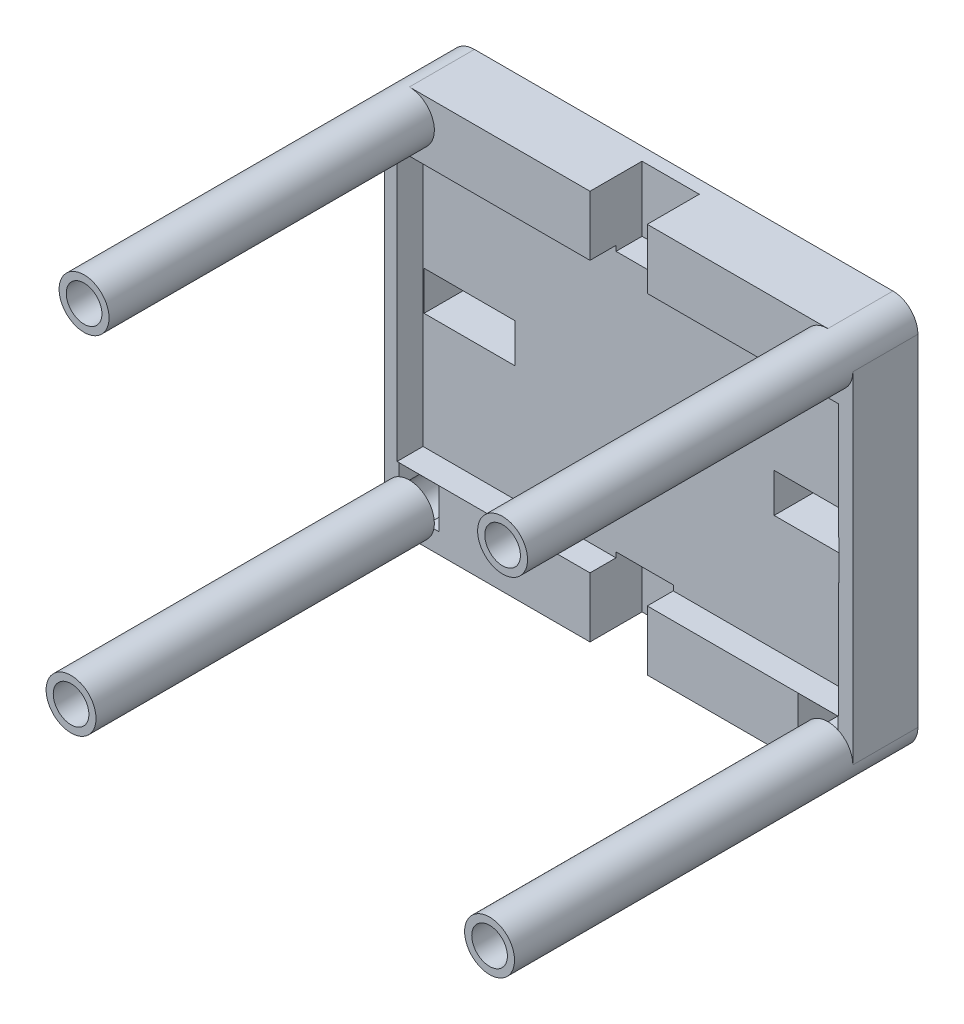
SolidWorks part; units mm, degrees
ref_plane "Front Plane" through (0, 0, 0) normal (0, 0, 1) x (1, 0, 0)
ref_plane "Top Plane" through (0, 0, 0) normal (0, 1, 0) x (1, 0, 0)
ref_plane "Right Plane" through (0, 0, 0) normal (1, 0, 0) x (0, 0, -1)
other "Configuration Table"
sketch "草图1" plane through (0, 0, 0) normal (0, 0, 1) x (1, 0, 0)
  line L0 (0, 0) -> (83.8895, 0) construction
  line L1 (-80.4073, 75) -> (80.4073, 75)
  line L2 (-90, 65.4073) -> (-90, -65.4073)
  line L3 (-80.4073, -75) -> (80.4073, -75)
  line L4 (90, 65.4073) -> (90, -65.4073)
  line L5 (-90, 75) -> (90, -75) construction
  line L6 (-90, -75) -> (90, 75) construction
  line L7 (0, 0) -> (0, -55.7173) construction
  line L8 (-85.1459, 52) -> (-7.782, 52)
  line L9 (-85.1459, -52) -> (-7.782, -52)
  line L10 (-85.1459, 52) -> (-85.1459, -52)
  line L11 (84.4384, -52) -> (84.4384, 52)
  line L14 (7.782, 52) -> (84.4384, 52)
  line L15 (7.782, -52) -> (84.4384, -52)
  line L16 (-46.464, 52) -> (-46.464, -52) construction
  line L17 (46.1102, -52) -> (46.1102, 52) construction
  line L18 (-7.782, 52) -> (7.782, 52)
  line L20 (-7.782, -52) -> (7.782, -52)
  line L21 (-49.7645, 7.5) -> (-49.7645, -7.5)
  line L22 (84.7645, 7.5) -> (49.7645, 7.5)
  line L23 (84.7645, 7.5) -> (84.7645, -7.5)
  line L24 (84.7645, -7.5) -> (49.7645, -7.5)
  line L25 (49.7645, 7.5) -> (49.7645, -7.5)
  line L26 (84.7645, 7.5) -> (49.7645, -7.5) construction
  line L27 (84.7645, -7.5) -> (49.7645, 7.5) construction
  line L28 (-84.7645, -7.5) -> (-49.7645, -7.5)
  line L29 (-84.7645, 7.5) -> (-49.7645, 7.5)
  line L30 (-84.7645, 7.5) -> (-84.7645, -7.5)
  line L31 (84.3918, -67.3175) -> (68.9601, -67.3175)
  line L32 (11, -50) -> (-11, -50)
  line L33 (11, -50) -> (11, -75)
  line L34 (11, -75) -> (-11, -75)
  line L35 (-11, -50) -> (-11, -75)
  line L36 (11, -50) -> (-11, -75) construction
  line L37 (11, -75) -> (-11, -50) construction
  line L38 (-84.3918, -52.0059) -> (-68.9601, -52.0059)
  line L39 (-84.3918, -52.0059) -> (-84.3918, -67.3175)
  line L40 (-84.3918, -67.3175) -> (-68.9601, -67.3175)
  line L41 (-68.9601, -52.0059) -> (-68.9601, -67.3175)
  line L42 (-84.3918, -52.0059) -> (-68.9601, -67.3175) construction
  line L43 (-84.3918, -67.3175) -> (-68.9601, -52.0059) construction
  line L44 (68.9601, -52.0059) -> (68.9601, -67.3175)
  line L45 (84.3918, -52.0059) -> (84.3918, -67.3175)
  line L46 (84.4384, -52) -> (84.3918, -52.0059)
  line L47 (68.9601, -52.0059) -> (84.3918, -52.0059)
  arc A1 (-80.4073, 75) -> (-90, 65.4073) centre (-80.4073, 65.4073) ccw
  arc A2 (80.4073, 75) -> (90, 65.4073) centre (80.4073, 65.4073) cw
  arc A3 (-80.4073, -75) -> (-90, -65.4073) centre (-80.4073, -65.4073) cw
  arc A4 (80.4073, -75) -> (90, -65.4073) centre (80.4073, -65.4073) ccw
  circle A9 centre (-80.4073, 65.4073) radius 9.5927
  circle A10 centre (80.4073, 65.4073) radius 9.5927
  circle A11 centre (-80.4073, -65.4073) radius 9.5927
  circle A12 centre (80.4073, -65.4073) radius 9.5927
  circle A17 centre (-80.4073, 65.4073) radius 6.851
  circle A18 centre (80.4073, 65.4073) radius 6.851
  circle A19 centre (-80.4073, -65.4073) radius 6.851
  circle A20 centre (80.4073, -65.4073) radius 6.851
  point P0 (0, 0)
  point P34 (67.2645, 0)
  point P43 (0, -62.5)
  point P55 (-76.676, -59.6617)
  point P62 (84.3918, -68.7337)
  dimension "D4" = 22
  dimension "D2" = 35
  dimension "D1" = 25
  dimension "D3" = 52
extrude "凸台-拉伸1" add sketch "草图1" along normal blind 25 contours A12 L4 A10 L1 A9 L2 A11 L3 L35 L9 L10 L8 L18 L14 L11 L22 L23 L24 L15 L33 region at (0, 72.6569, 0)
extrude "凸台-拉伸2" add sketch "草图1<17>" along normal blind 150 contours A11 A3 A19 | A1 A9 A17 | A10 A2 A18 | A4 A12 A20 region at (-73.8162, 71.9985, 0) region at (86.9985, 71.9985, 0) region at (-88.2551, -60.3636, 0) region at (87.0038, -72.0038, 0)
sketch "草图1<17>" plane through (0, 0, 0) normal (0, 0, 1) x (1, 0, 0) same geometry as "草图1"
extrude "凸台-拉伸3" add sketch "草图1<20>" along normal blind 15 contours L35 L32 L33 L15 L11 L24 L25 L22 L14 L18 L8 L10 L9 L30 L29 L21 L28 region at (-0.352, 0.1356, 0)
sketch "草图1<20>" plane through (0, 0, 0) normal (0, 0, 1) x (1, 0, 0) same geometry as "草图1"
extrude "凸台-拉伸4" add sketch "草图1<21>" along normal blind 25 contours A12 L31 L44 L47 L46 L15 L33 L3 region at (40.7678, -63.7139, 0)
sketch "草图1<21>" plane through (0, 0, 0) normal (0, 0, 1) x (1, 0, 0) same geometry as "草图1"
ref_plane "基准面1" through (0, 0, 25) normal (0, 0, -1) x (-1, 0, 0)
sketch "草图2" plane through (0, 0, 25) normal (0, 0, -1) x (-1, 0, 0)
  line L0 (0, 0) -> (135.6072, 0) construction
  line L1 (-11, -75) -> (11, -75)
  line L2 (-11, -75) -> (-11, -50)
  line L3 (-11, -50) -> (11, -50)
  line L4 (11, -75) -> (11, -50)
  line L5 (-11, 75) -> (11, 75)
  line L6 (11, 75) -> (11, 50)
  line L7 (-11, 50) -> (11, 50)
  line L8 (-11, 75) -> (-11, 50)
  circle A0 centre (-80.4073, -65.4073) radius 6.851
  circle A1 centre (80.4073, -65.4073) radius 6.851
ref_plane "基准面2" through (0, 0, 155) normal (0, 0, -1) x (-1, 0, 0)
sketch "草图4" plane through (0, 0, 155) normal (0, 0, -1) x (-1, 0, 0)
  circle A0 centre (80.4073, -65.4073) radius 9.5927
  circle A1 centre (-80.4073, -65.4073) radius 9.5927
  circle A2 centre (80.4073, -65.4073) radius 6.851
  circle A3 centre (-80.4073, -65.4073) radius 6.851
extrude "凸台-拉伸6" add sketch "草图4" along normal blind 130
extrude "切除-拉伸3" cut sketch "草图2" against normal mid plane 40
extrude "凸台-拉伸7" add sketch "草图1<24>" along normal blind 5 contours L32 L35 L9 L20 L15 L33 | L9 L35 L3 L33 L15 L20 region at (0, -63.5, 0) region at (0, -51, 0)
sketch "草图1<24>" plane through (0, 0, 0) normal (0, 0, 1) x (1, 0, 0) same geometry as "草图1"
